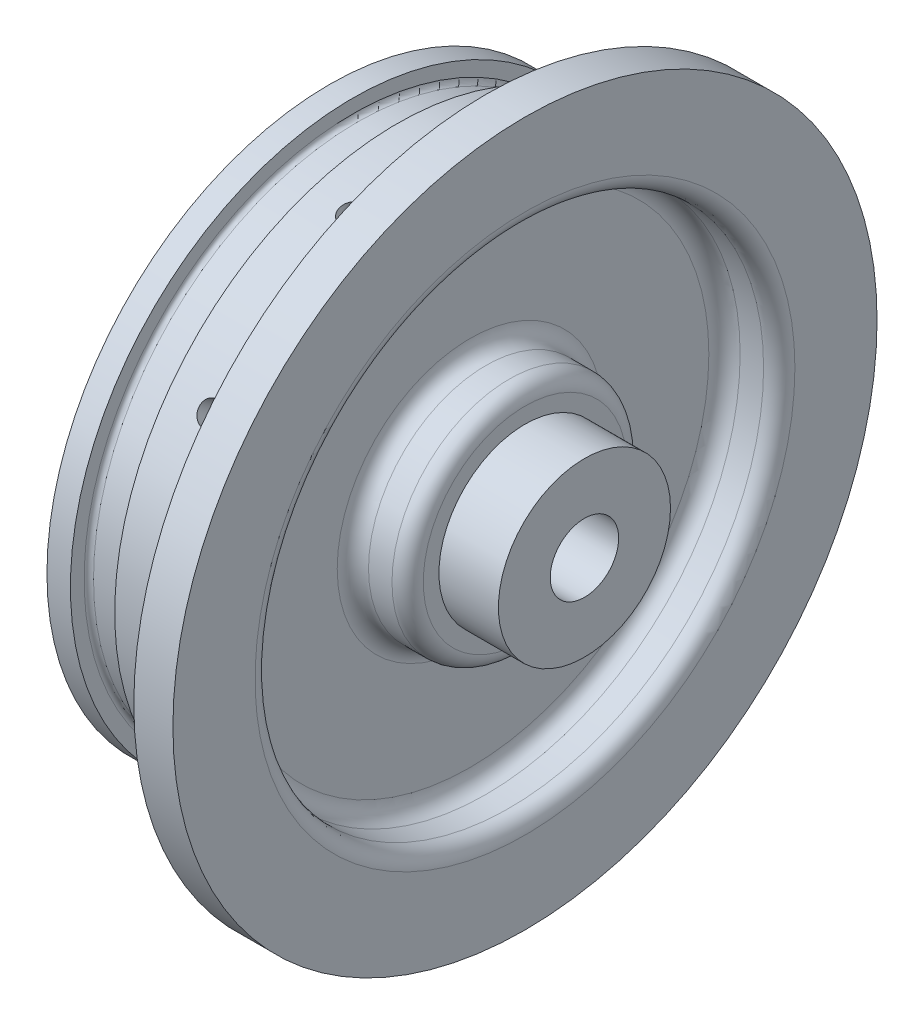
SolidWorks part; units mm, degrees
material "7075-T6 (SN)"
ref_plane "Front Plane" through (0, 0, 0) normal (0, 0, 1) x (1, 0, 0)
ref_plane "Top Plane" through (0, 0, 0) normal (0, 1, 0) x (1, 0, 0)
ref_plane "Right Plane" through (0, 0, 0) normal (1, 0, 0) x (0, 0, -1)
sketch "Sketch1" plane through (0, 0, 0) normal (1, 0, 0) x (0, 0, -1)
  circle A0 centre (0, 0) radius 57.15
  dimension "D1" = 114.3
extrude "Boss-Extrude1" add sketch "Sketch1" along normal blind 6.35
sketch "Sketch2" plane through (0, 0, 0) normal (-1, 0, 0) x (0, 0, 1)
  circle A0 centre (0, 0) radius 45.847
  dimension "D1" = 91.694
extrude "Boss-Extrude2" add sketch "Sketch2" along normal blind 25.4
sketch "Sketch10" plane through (0, 0, 0) normal (0, 1, 0) x (1, 0, 0)
  line L0 (0, 0) -> (-53.2238, 0) construction
  line L1 (-26.2636, 0) -> (26.2636, 0) construction
  line L2 (0, 0) -> (0, 64.5447) construction
  line L3 (0, -62.865) -> (0, 62.865) construction
ref_plane "Plane1" through (0, 0, -45.847) normal (0, 0, -1) x (-1, 0, 0)
sketch "Sketch11" plane through (0, 0, -45.847) normal (0, 0, -1) x (-1, 0, 0)
  line L0 (0, 0) -> (53.2238, 0) construction
  line L1 (0, -45.847) -> (0, 45.847) construction
  circle A0 centre (7.62, 0) radius 1.8986
  dimension "D2" = 3.7973
  dimension "D1" = 7.62
extrude "Cut-Extrude3" cut sketch "Sketch11" against normal blind 10.16
pattern_circular "CirPattern1" count 10 every 36 about axis through (0, 0, 0) along (-1, 0, 0) of "Cut-Extrude3" reverse direction yes
sketch "Sketch15" plane through (6.35, 0, 0) normal (1, 0, 0) x (0, 0, -1)
  circle A0 centre (0, 0) radius 5.5562
  dimension "D1" = 11.1125
extrude "Cut-Extrude4" cut sketch "Sketch15" against normal through all both and the other way through all
sketch "Sketch16" plane through (0, 0, 0) normal (0, 0, 1) x (1, 0, 0)
  line L0 (0, 45.847) -> (-25.4, 45.847) construction
  line L1 (-21.59, 45.847) -> (-14.4018, 45.847)
  line L2 (-21.59, 45.847) -> (-21.59, 43.6245)
  line L3 (-20.828, 42.8625) -> (-15.1638, 42.8625)
  line L4 (-14.4018, 45.847) -> (-14.4018, 43.6245)
  line L5 (0, 0) -> (-53.2238, 0) construction
  line L6 (-25.4, 45.847) -> (-25.4, -45.847) construction
  arc A0 (-14.4018, 43.6245) -> (-15.1638, 42.8625) centre (-15.1638, 43.6245) cw
  arc A1 (-20.828, 42.8625) -> (-21.59, 43.6245) centre (-20.828, 43.6245) cw
  point P8 (-26.6119, 0)
  point P13 (-14.4018, 42.8625)
  point P16 (-21.59, 42.8625)
  dimension "D4" = 0.762
  dimension "D1" = 42.8625
  dimension "D2" = 3.81
  dimension "D3" = 7.1882
revolve "Cut-Revolve1" cut sketch "Sketch16" angle 360 about L0
sketch "Sketch17" plane through (6.35, 0, 0) normal (1, 0, 0) x (0, 0, -1)
  circle A0 centre (0, 0) radius 13.97
  circle A1 centre (0, 0) radius 5.5562
  dimension "D1" = 27.94
  dimension "D2" = 11.1125
extrude "Boss-Extrude3" add sketch "Sketch17" along normal blind 9.652
sketch "Sketch18" plane through (0, 0, 0) normal (0, 0, 1) x (1, 0, 0)
  line L0 (6.35, -57.15) -> (6.35, 57.15) construction
  line L1 (6.35, 41.275) -> (-2.54, 41.275)
  line L2 (6.35, 41.275) -> (6.35, 19.05)
  line L3 (6.35, 19.05) -> (-2.54, 19.05)
  line L4 (-2.54, 41.275) -> (-2.54, 19.05)
  line L5 (0, 0) -> (-53.2238, 0) construction
  dimension "D1" = 8.89
  dimension "D2" = 19.05
  dimension "D3" = 41.275
revolve "Cut-Revolve2" cut sketch "Sketch18" angle 360 about L0
fillet "Fillet1" radius 2.54 4 edges at (6.35, 0, -41.275) (-2.54, 0, -41.275) (-2.54, 0, -19.05) (6.35, 0, -19.05)
